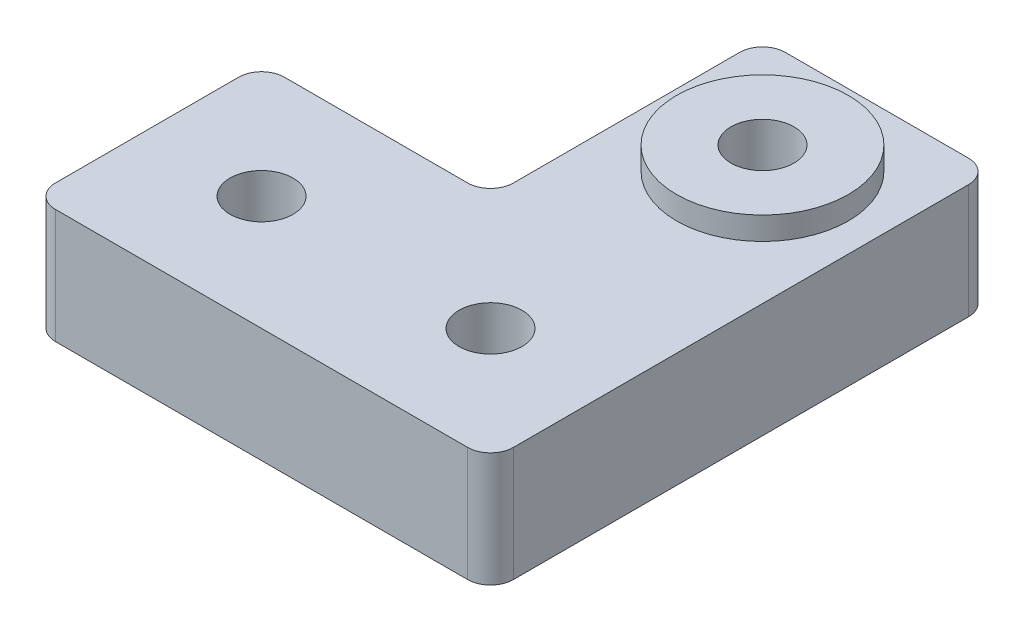
SolidWorks part; units mm, degrees
ref_plane "Front Plane" through (0, 0, 0) normal (0, 0, 1) x (1, 0, 0)
ref_plane "Top Plane" through (0, 0, 0) normal (0, 1, 0) x (1, 0, 0)
ref_plane "Right Plane" through (0, 0, 0) normal (1, 0, 0) x (0, 0, -1)
sketch "Sketch1" plane through (0, 0, 0) normal (0, 1, 0) x (1, 0, 0)
  line L0 (0, 0) -> (40, 0)
  line L1 (40, 0) -> (40, 43.75)
  line L2 (40, 43.75) -> (20, 43.75)
  line L3 (20, 43.75) -> (20, 20)
  line L4 (20, 20) -> (0, 20)
  line L5 (0, 20) -> (0, 0)
  dimension "D1" = 20
  dimension "D2" = 40
  dimension "D3" = 20
  dimension "D4" = 23.75
extrude "Boss-Extrude1" add sketch "Sketch1" along normal blind 10
sketch "Sketch2" plane through (0, 0, 0) normal (0, -1, 0) x (1, 0, 0)
  line L0 (0, -10) -> (40, -10)
  line L1 (0, -20) -> (0, 0) construction
  line L2 (40, 0) -> (40, -43.75) construction
  point P6 (10, -10)
  point P7 (30, -10)
  dimension "D1" = 10
  dimension "D2" = 10
hole_wizard "CBORE for M5 SHCS1" positions "Sketch3" profile "Sketch4" counterbore size "M5" standard "ANSI Metric" end condition through all
sketch "Sketch3" plane through (0, 0, 0) normal (0, -1, 0) x (-1, 0, 0)
  point P0 (-10, 10)
  point P3 (-30, 10)
sketch "Sketch4" plane through (10, 0, -10) normal (1, 0, 0) x (0, 0, -1)
  line L0 (0, 0) -> (0, 10)
  line L1 (0, 10) -> (2.75, 10)
  line L3 (2.75, 10) -> (2.75, 5)
  line L4 (5, 5) -> (2.75, 5)
  line L5 (5, 5) -> (5, 0.025)
  line L6 (5, 0.025) -> (5.025, 0)
  line L7 (5.025, 0) -> (0, 0)
  line L8 (-5, 0.025) -> (-5.025, 0) construction
  line L11 (0, -6.35) -> (0, 107.95) construction
  dimension "Thru Hole Dia." = 5.5
  dimension "Thru Hole Depth" = 10
  dimension "C'Bore Dia." = 10
  dimension "C'Bore Depth" = 5
  dimension "Near C'Sink Dia." = 10.05
  dimension "Near C'Sink Angle" = 90
fillet "Fillet1" radius 2 6 edges at (20, 5, -20) (20, 5, -43.75) (40, 5, -43.75) (0, 5, -20) (0, 5, 0) (40, 5, 0)
sketch "Sketch5" plane through (0, 10, 0) normal (0, 1, 0) x (1, 0, 0)
  line L0 (30, 43.75) -> (30, 0) construction
  line L1 (38, 43.75) -> (22, 43.75) construction
  line L2 (2, 0) -> (38, 0) construction
  line L3 (20, 33.75) -> (40, 33.75) construction
  circle A0 centre (30, 33.75) radius 1.5
  dimension "D1" = 3
  dimension "D2" = 10
sketch "Sketch6" plane through (0, 0, 0) normal (0, -1, 0) x (1, 0, 0)
  line L0 (38, -43.75) -> (22, -43.75) construction
  line L1 (34.7, -33.75) -> (32.35, -29.6797)
  line L2 (32.35, -29.6797) -> (27.65, -29.6797)
  line L3 (27.65, -29.6797) -> (25.3, -33.75)
  line L4 (25.3, -33.75) -> (27.65, -37.8203)
  line L5 (27.65, -37.8203) -> (32.35, -37.8203)
  line L6 (32.35, -37.8203) -> (34.7, -33.75)
  circle A0 centre (30, -33.75) radius 4.0703 construction
  point P1 (0, 0)
  dimension "D1" = 4.7
extrude "Cut-Extrude1" cut sketch "Sketch6" against normal blind 4.2
hole_wizard "M5 Clearance Hole1" positions "Sketch7" profile "Sketch8" hole size "M5" standard "ANSI Metric" end condition through all
sketch "Sketch7" plane through (0, 0, 0) normal (0, -1, 0) x (-1, 0, 0)
  point P0 (-30, 33.75)
sketch "Sketch8" plane through (30, 0, -33.75) normal (1, 0, 0) x (0, 0, -1)
  line L0 (0, 0) -> (0, 10)
  line L1 (0, 10) -> (2.75, 10)
  line L2 (2.75, 10) -> (2.75, 0.025)
  line L3 (2.75, 0.025) -> (2.775, 0)
  line L5 (2.775, 0) -> (0, 0)
  line L6 (-2.75, 0.025) -> (-2.775, 0) construction
  line L11 (0, -6.35) -> (0, 107.95) construction
  dimension "Thru Hole Dia." = 5.5
  dimension "Thru Hole Depth" = 10
  dimension "Near C'Sink Dia." = 5.55
  dimension "Near C'Sink Angle" = 90
sketch "Sketch9" plane through (0, 10, 0) normal (0, 1, 0) x (1, 0, 0)
  circle A0 centre (30, 33.75) radius 2.75 construction
  circle A1 centre (30, 33.75) radius 2.75
  circle A2 centre (30, 33.75) radius 7.5
  dimension "D1" = 15
extrude "Boss-Extrude2" add sketch "Sketch9" along normal blind 2
